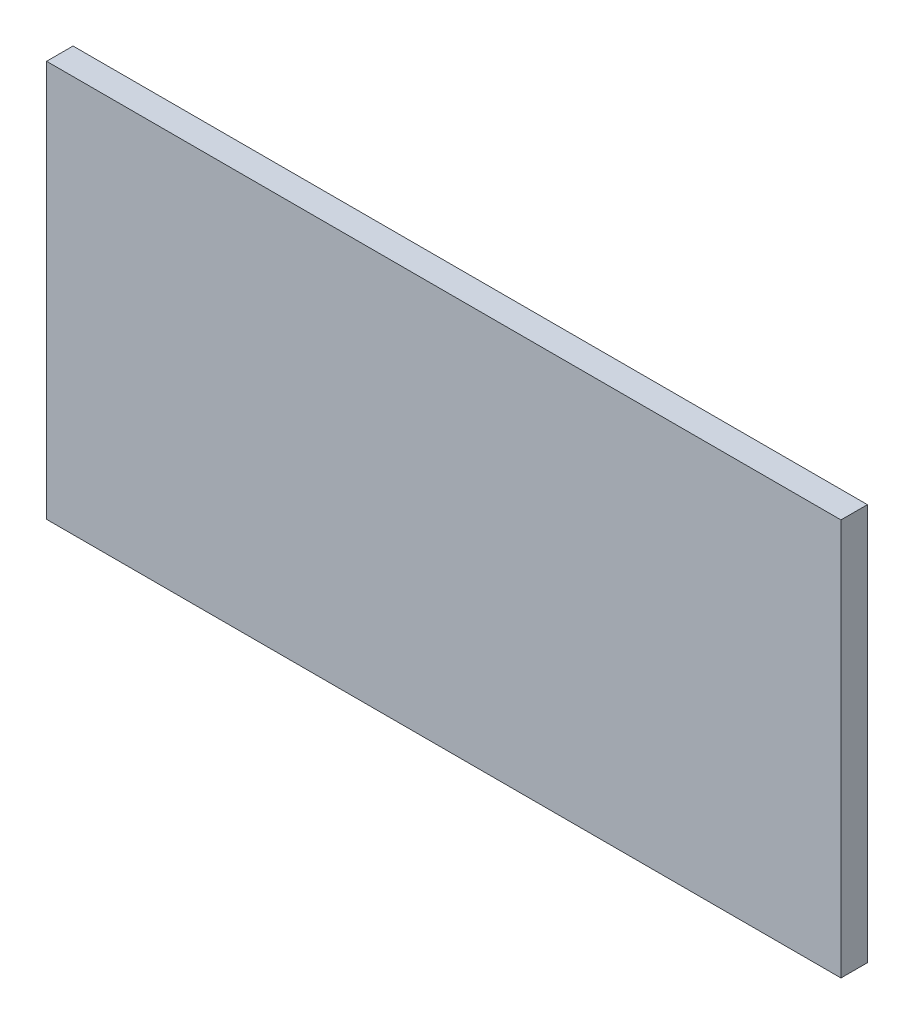
SolidWorks part; units mm, degrees
ref_plane "Front Plane" through (0, 0, 0) normal (0, 0, 1) x (1, 0, 0)
ref_plane "Top Plane" through (0, 0, 0) normal (0, 1, 0) x (1, 0, 0)
ref_plane "Right Plane" through (0, 0, 0) normal (1, 0, 0) x (0, 0, -1)
sketch "Sketch1" plane through (0, 0, 0) normal (0, 0, 1) x (1, 0, 0)
  line L1 (-150.18, 75) -> (150.18, 75)
  line L2 (-150.18, 75) -> (-150.18, -75)
  line L3 (-150.18, -75) -> (150.18, -75)
  line L4 (150.18, 75) -> (150.18, -75)
  line L5 (-150.18, 75) -> (150.18, -75) construction
  line L6 (-150.18, -75) -> (150.18, 75) construction
  point P0 (0, 0)
  dimension "D1" = 300.36
  dimension "D2" = 150
extrude "Boss-Extrude1" add sketch "Sketch1" along normal blind 10
